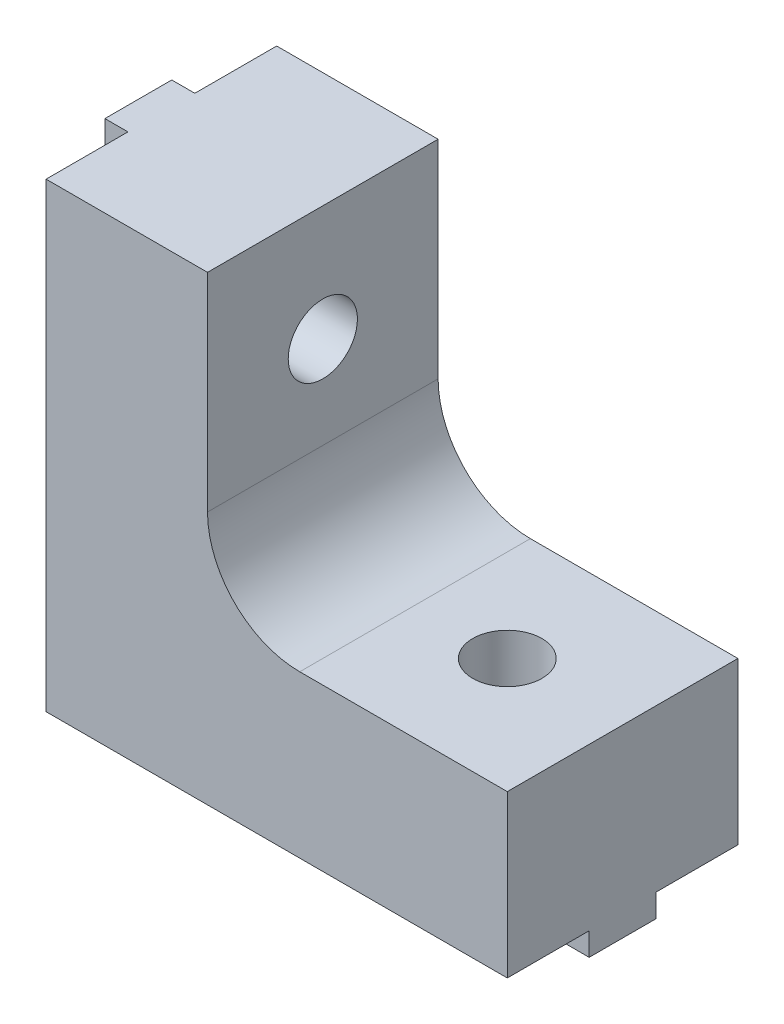
SolidWorks part; units mm, degrees
ref_plane "Front Plane" through (0, 0, 0) normal (0, 0, 1) x (1, 0, 0)
ref_plane "Top Plane" through (0, 0, 0) normal (0, 1, 0) x (1, 0, 0)
ref_plane "Right Plane" through (0, 0, 0) normal (1, 0, 0) x (0, 0, -1)
sketch "Esquisse1" plane through (0, 0, 0) normal (0, 0, 1) x (1, 0, 0)
  line L0 (0, 0) -> (20, 0)
  line L1 (20, 0) -> (20, 7)
  line L2 (20, 7) -> (11, 7)
  line L4 (7, 11) -> (7, 20)
  line L5 (7, 20) -> (0, 20)
  line L6 (0, 20) -> (0, 0)
  arc A0 (11, 7) -> (7, 11) centre (11, 11) cw
  dimension "D1" = 4
  dimension "D2" = 20
  dimension "D3" = 7
extrude "Main" add sketch "Esquisse1" along normal blind 10
sketch "Esquisse4" plane through (0, 0, 0) normal (-1, 0, 0) x (0, 0, 1)
  line L0 (10, 20) -> (0, 20) construction
  line L1 (3.55, 20) -> (6.45, 20)
  line L2 (3.55, 20) -> (3.55, 0)
  line L3 (3.55, 0) -> (6.45, 0)
  line L4 (6.45, 20) -> (6.45, 0)
  line L5 (10, 0) -> (0, 0) construction
  point P8 (5, 20)
  point P9 (5, 20)
  dimension "D1" = 2.9
extrude "MakerBeamFixVertical" add sketch "Esquisse4" along normal blind 1
sketch "Esquisse2" plane through (0, 0, 0) normal (-1, 0, 0) x (0, 0, 1)
  line L0 (10, 20) -> (6.45, 20) construction
  line L1 (10, 20) -> (0, 20) construction
  circle A0 centre (5, 15) radius 1.5
  point P9 (5, 20)
  dimension "D1" = 3
  dimension "D2" = 5
extrude "MakerBeamVerticalHole" cut sketch "Esquisse2" against normal through all both and the other way through all
sketch "Esquisse5" plane through (0, 0, 0) normal (0, -1, 0) x (-1, 0, 0)
  line L0 (-20, -10) -> (-20, 0) construction
  line L1 (0, -3.55) -> (-20, -3.55)
  line L2 (0, -3.55) -> (0, -6.45)
  line L3 (0, -6.45) -> (-20, -6.45)
  line L4 (-20, -3.55) -> (-20, -6.45)
  line L5 (1, -6.45) -> (0, -6.45) construction
extrude "MakerBeamFixHorizontal" add sketch "Esquisse5" along normal blind 1
sketch "Esquisse3" plane through (0, 0, 0) normal (0, -1, 0) x (1, 0, 0)
  line L0 (20, 10) -> (20, 6.45) construction
  circle A0 centre (15, 5) radius 1.5
  dimension "D2" = 5
extrude "MakerBeamHorizontalHole" cut sketch "Esquisse3" against normal through all both and the other way through all
